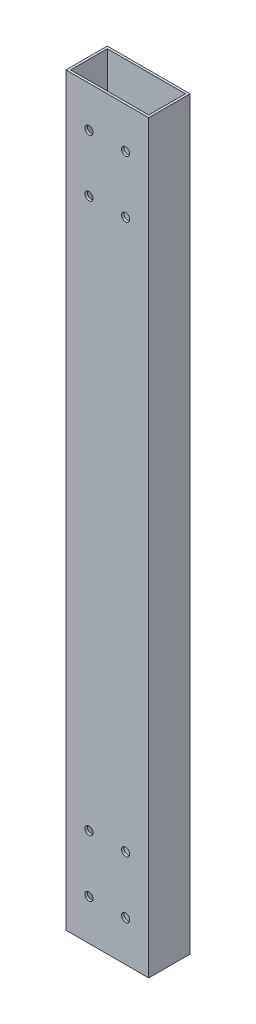
SolidWorks part; units mm, degrees
material "Thornel VCB-20 Carbon Cloth"
ref_plane "Front Plane" through (0, 0, 0) normal (0, 0, 1) x (1, 0, 0)
ref_plane "Top Plane" through (0, 0, 0) normal (0, 1, 0) x (1, 0, 0)
ref_plane "Right Plane" through (0, 0, 0) normal (1, 0, 0) x (0, 0, -1)
sketch "Sketch1" plane through (0, 0, 0) normal (0, 1, 0) x (1, 0, 0)
  line L0 (-25.4, 0) -> (-28.575, 0) construction
  line L1 (-25.4, -12.7) -> (25.4, -12.7)
  line L2 (-25.4, -12.7) -> (-25.4, 12.7)
  line L3 (-25.4, 12.7) -> (25.4, 12.7)
  line L4 (25.4, -12.7) -> (25.4, 12.7)
  line L5 (-25.4, -12.7) -> (25.4, 12.7) construction
  line L6 (-25.4, 12.7) -> (25.4, -12.7) construction
  line L11 (-23.95, 11.25) -> (23.95, 11.25)
  line L12 (23.95, -11.25) -> (23.95, 11.25)
  line L13 (0, -12.7) -> (0, -15.875) construction
  line L14 (-23.95, -11.25) -> (23.95, -11.25)
  line L15 (-23.95, -11.25) -> (-23.95, 11.25)
  point P0 (0, 0)
  point P6 (0, 0)
  dimension "D2" = 50.8
  dimension "D3" = 1.45
extrude "Boss-Extrude1" add sketch "Sketch1" along normal blind 457.2
sketch "Sketch2" plane through (0, 0, 15.875) normal (0, 0, 1) x (1, 0, 0)
  line L1 (-11.25, 25) -> (11.25, 25) construction
  line L2 (-11.25, 25) -> (-11.25, 60) construction
  line L3 (-11.25, 60) -> (11.25, 60) construction
  line L4 (11.25, 25) -> (11.25, 60) construction
  circle A0 centre (-11.25, 60) radius 2.5
  circle A1 centre (-11.25, 25) radius 2.5
  circle A2 centre (11.25, 25) radius 2.5
  circle A3 centre (11.25, 60) radius 2.5
  point P4 (0, 25)
  dimension "D4" = 5
  dimension "D1" = 22.5
  dimension "D2" = 35
  dimension "D3" = 25
extrude "Cut-Extrude1" cut sketch "Sketch2" against normal through all
ref_plane "Plane1" through (0, 228.6, 0) normal (0, -1, 0) x (-1, 0, 0)
mirror "Mirror1" about plane through (0, 228.6, 0) normal (0, -1, 0) of "Cut-Extrude1"
equation "\"tube_width\"= 1in"
equation "\"tube_height\"= 2in"
equation "\"tube_thickness\"= 0.125in"
equation "\"tube_length\"= 1.5ft"
equation "\"D1@Boss-Extrude1\"=\"tube_length\""
equation "\"D1@Sketch1\"=\"tube_width\""
equation "\"D2@Sketch1\"=\"tube_height\""
